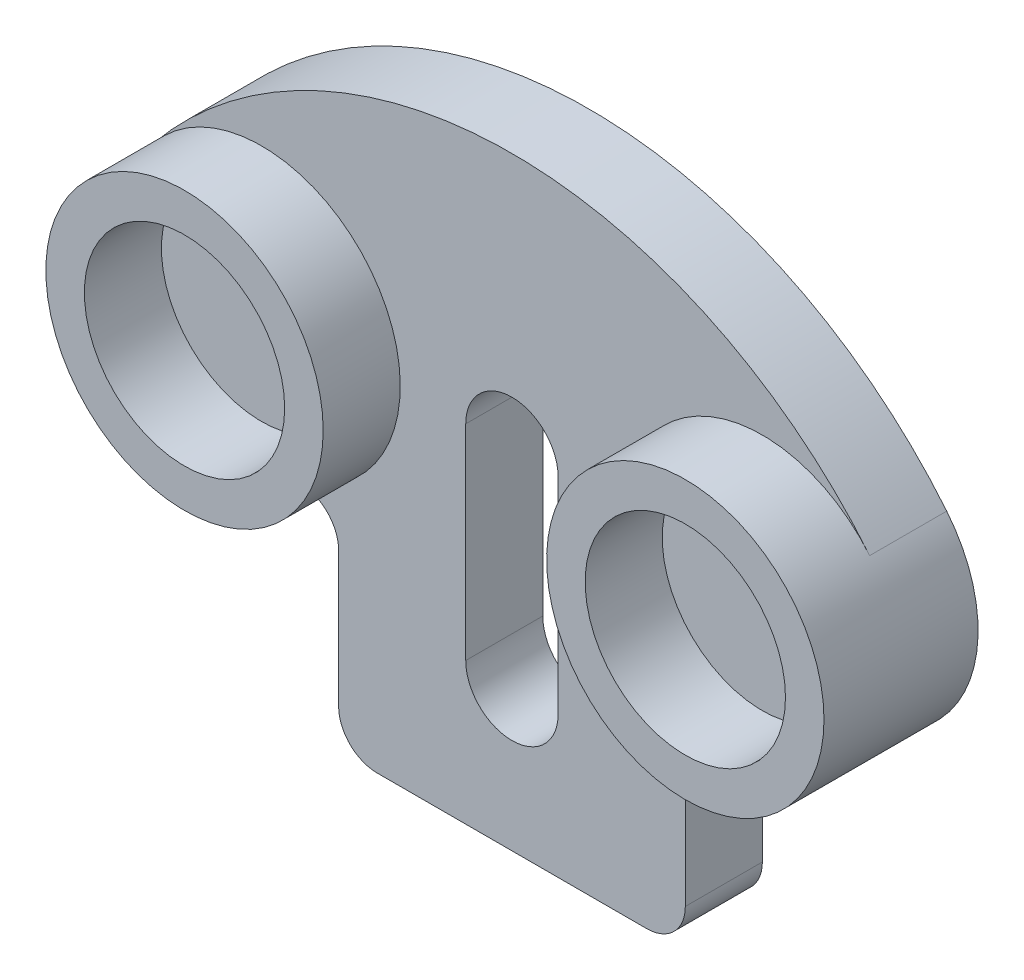
SolidWorks part; units mm, degrees
ref_plane "Front Plane" through (0, 0, 0) normal (0, 0, 1) x (1, 0, 0)
ref_plane "Top Plane" through (0, 0, 0) normal (0, 1, 0) x (1, 0, 0)
ref_plane "Right Plane" through (0, 0, 0) normal (1, 0, 0) x (0, 0, -1)
sketch "Sketch1" plane through (0, 0, 0) normal (0, 0, 1) x (1, 0, 0)
  line L0 (55, 0) -> (-55, 0) construction
  line L1 (-6, 0) -> (-6, 26.6036)
  line L2 (6, 26.6036) -> (6, 0)
  line L3 (0, -55) -> (0, 55) construction
  line L4 (17.5, -18.3964) -> (-17.5, -18.3964)
  line L5 (22.5, -13.3964) -> (22.5, 4.1536)
  line L6 (22.5, 26.6036) -> (-22.5, 26.6036) construction
  line L7 (-22.5, -13.3964) -> (-22.5, 4.1536)
  line L8 (-32.5, 26.6036) -> (32.5, 26.6036) construction
  arc A0 (6, 0) -> (-6, 0) centre (0, 0) cw
  arc A1 (-6, 26.6036) -> (6, 26.6036) centre (0, 26.6036) cw
  circle A2 centre (32.5, 26.6036) radius 18
  circle A3 centre (32.5, 26.6036) radius 13
  arc A4 (46.4286, 38.0051) -> (-46.4286, 38.0051) centre (0, 0) ccw
  circle A5 centre (-32.5, 26.6036) radius 13
  circle A6 centre (-32.5, 26.6036) radius 18
  arc A7 (-22.5, 4.1536) -> (-28.587, 9.034) centre (-27.5, 4.1536) ccw
  arc A8 (28.587, 9.034) -> (22.5, 4.1536) centre (27.5, 4.1536) ccw
  arc A9 (17.5, -18.3964) -> (22.5, -13.3964) centre (17.5, -13.3964) ccw
  arc A10 (-17.5, -18.3964) -> (-22.5, -13.3964) centre (-17.5, -13.3964) cw
  point P9 (0, -18.3964)
  point P19 (0, 26.6036)
  point P31 (22.5, -18.3964)
  point P34 (-22.5, -18.3964)
  dimension "D2" = 45
  dimension "D5" = 36
  dimension "D6" = 5
  dimension "D7" = 120
  dimension "D8" = 10
  dimension "D9" = 10
  dimension "D10" = 5
  dimension "D1" = 12
  dimension "D3" = 45
  dimension "D4" = 65
  dimension "D11" = 45
extrude "Boss-Extrude1" add sketch "Sketch1" along normal blind 10 contours A10 L4 A9 L5 A8 A2 A4 A6 A7 L7 L1 A1 L2 A0 | A6 A5 | A5 | A3 | A2 A3 region at (0, -17.1812, 0) region at (17.6068, 35.7754, 0) region at (-47.3932, 17.4317, 0) region at (32.5, 26.6036, 0) region at (-32.5, 26.6036, 0)
extrude "Boss-Extrude2" add sketch "Sketch1<3>" along normal blind 10 from surface contours A6 A5 | A2 A3 region at (17.6068, 35.7754, 0) region at (-47.3932, 17.4317, 0) starting at face at (0, 4.8935, 10)
sketch "Sketch1<3>" plane through (0, 0, 0) normal (0, 0, 1) x (1, 0, 0) same geometry as "Sketch1"
